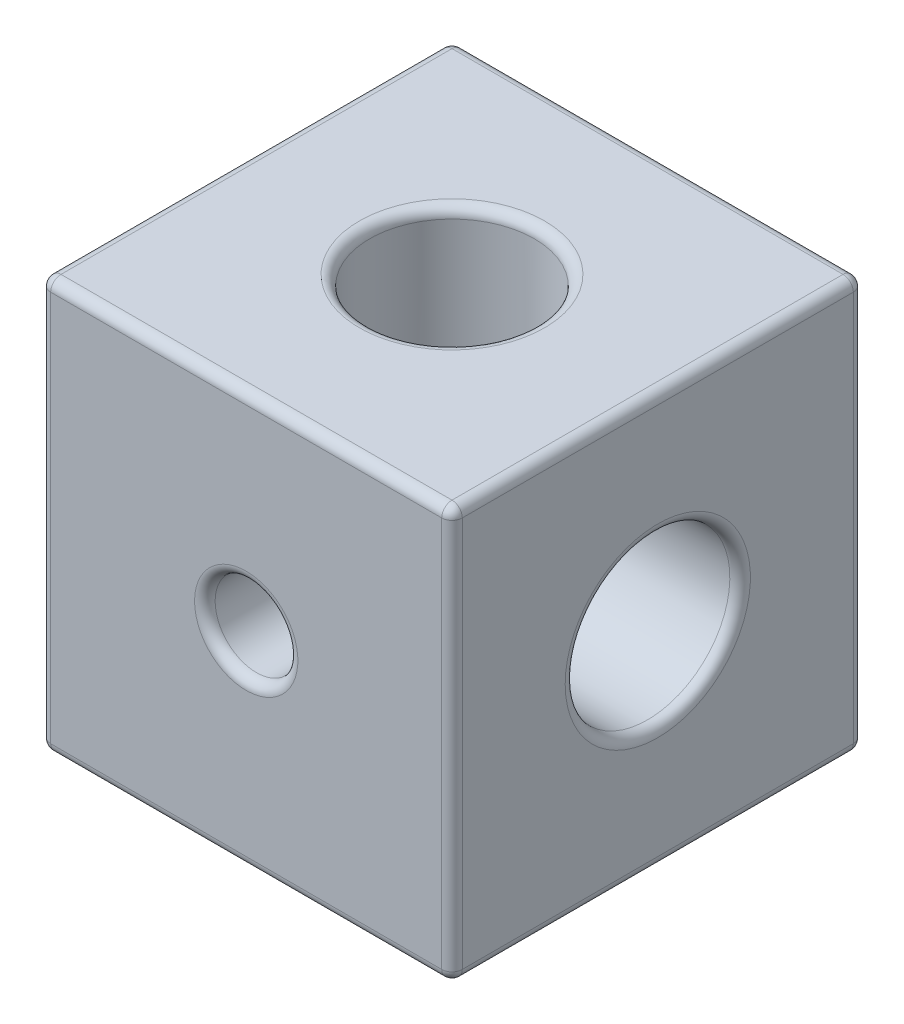
SolidWorks part; units mm, degrees
ref_plane "Front Plane" through (0, 0, 0) normal (0, 0, 1) x (1, 0, 0)
ref_plane "Top Plane" through (0, 0, 0) normal (0, 1, 0) x (1, 0, 0)
ref_plane "Right Plane" through (0, 0, 0) normal (1, 0, 0) x (0, 0, -1)
sketch "Sketch1" plane through (0, 0, 0) normal (0, 0, 1) x (1, 0, 0)
  line L1 (0, 0) -> (25.4, 0)
  line L2 (0, 0) -> (0, 25.4)
  line L3 (0, 25.4) -> (25.4, 25.4)
  line L4 (25.4, 0) -> (25.4, 25.4)
  dimension "D1" = 25.4
  dimension "D2" = 25.4
extrude "Boss-Extrude1" add sketch "Sketch1" along normal blind 25.4
hole_wizard "1/4-20 Tapped Hole1" positions "3DSketch3" profile "Sketch6" tap size "1/4-20" standard "ANSI Inch" end condition through all
sketch3d "3DSketch3"
  line L1 (12.7, 25.4, 25.4) -> (12.7, 0, 25.4) construction
  line L2 (25.4, 25.4, 25.4) -> (0, 25.4, 25.4) construction
  line L3 (0, 0, 25.4) -> (25.4, 0, 25.4) construction
  line L5 (25.4, 25.4, 12.7) -> (25.4, 0, 12.7) construction
  line L6 (25.4, 25.4, 25.4) -> (25.4, 25.4, 0) construction
  line L7 (25.4, 0, 25.4) -> (25.4, 0, 0) construction
  line L9 (0, 25.4, 12.7) -> (25.4, 25.4, 12.7) construction
  line L10 (0, 25.4, 25.4) -> (0, 25.4, 0) construction
  point P0 (12.7, 12.7, 25.4)
  point P2 (25.4, 12.7, 12.7)
  point P4 (12.7, 25.4, 12.7)
  point P31 (0, 0, 0)
cosmetic thread "Hole Thread1" parameters "D2"=6.35
cosmetic thread "Hole Thread2" parameters "D2"=6.35
cosmetic thread "Hole Thread3" parameters "D2"=6.35
sketch "Sketch6" plane through (12.7, 12.7, 25.4) normal (1, 0, 0) x (0, -1, 0)
  line L0 (0, 0) -> (0, 25.4)
  line L1 (0, 25.4) -> (2.5527, 25.4)
  line L2 (2.5527, 25.4) -> (2.5527, 0)
  line L5 (2.5527, 0) -> (0, 0)
  line L11 (0, -6.35) -> (0, 107.95) construction
  dimension "Thru Tap Drill Dia." = 5.1054
  dimension "Thru Tap Drill Depth" = 25.4
sketch "Sketch7" plane through (25.4, 0, 0) normal (1, 0, 0) x (0, 0, -1)
  circle A0 centre (-12.7, 12.7) radius 5.08
  dimension "D1" = 10.16
extrude "Cut-Extrude1" cut sketch "Sketch7" against normal blind 12.7
sketch "Sketch8" plane through (0, 0, 0) normal (0, 0, -1) x (-1, 0, 0)
  circle A0 centre (-12.7, 12.7) radius 5.08
  point P3 (-12.7, 12.7)
  dimension "D1" = 10.16
extrude "Cut-Extrude2" cut sketch "Sketch8" against normal blind 12.7
sketch "Sketch10" plane through (0, 25.4, 0) normal (0, 1, 0) x (1, 0, 0)
  circle A0 centre (12.7, -12.7) radius 5.08
  point P2 (0, 0)
  point P3 (6.8961, -14.1802)
  point P5 (12.7, -12.7)
  dimension "D1" = 10.16
extrude "Cut-Extrude3" cut sketch "Sketch10" against normal blind 12.7
fillet "Fillet1" radius 0.635 18 edges at (0, 12.7, 10.1473) (0, 0, 12.7) (12.7, 0, 15.2527) (12.7, 0, 0) (0, 12.7, 0) (7.62, 12.7, 0) (25.4, 0, 12.7) (25.4, 12.7, 0) (25.4, 12.7, 7.62) (15.2527, 12.7, 25.4) (25.4, 12.7, 25.4) (12.7, 0, 25.4) (0, 12.7, 25.4) (25.4, 25.4, 12.7) (12.7, 25.4, 25.4) (0, 25.4, 12.7) (12.7, 25.4, 0) (12.7, 25.4, 17.78)
